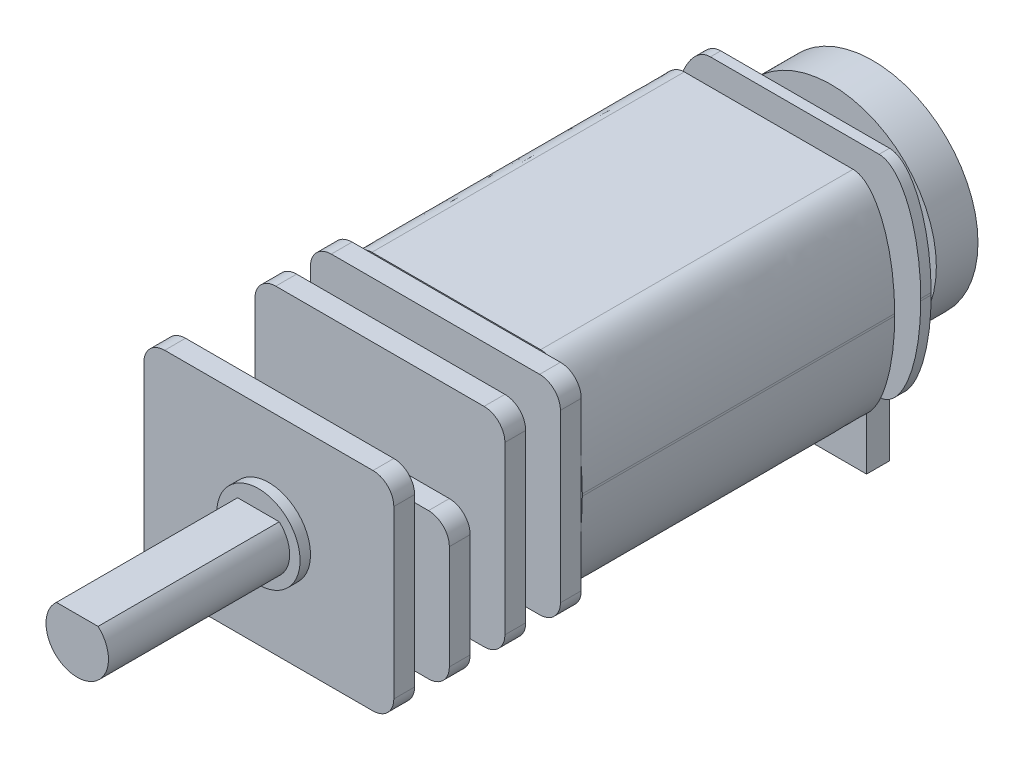
SolidWorks part; units mm, degrees
note: The reader was unsure of these and kept them because the rebuilt part matched: shared geometry of "Sketch1<3>", "Sketch2<3>", "Sketch2<5>".
ref_plane "Front Plane" through (0, 0, 0) normal (0, 0, 1) x (1, 0, 0)
ref_plane "Top Plane" through (0, 0, 0) normal (0, 1, 0) x (1, 0, 0)
ref_plane "Right Plane" through (0, 0, 0) normal (1, 0, 0) x (0, 0, -1)
sketch "Sketch1" plane through (0, 0, 0) normal (0, 0, 1) x (1, 0, 0)
  line L0 (1, 1.118) -> (-1, 1.118)
  circle A0 centre (0, 0) radius 1.5
  circle A1 centre (0, 0) radius 0.5
  dimension "D1" = 3
  dimension "D3" = 1
  dimension "D2" = 2
extrude "Boss-Extrude1" add sketch "Sketch1" along normal blind 8.7 contours L0 A0 | A1
extrude "Boss-Extrude3" add sketch "Sketch1<3>" against normal blind 38.2 from surface at 8.7 contours A1 starting at face at (0, -0.191, 8.7)
sketch "Sketch1<3>" plane through (0, 0, 0) normal (0, 0, 1) x (1, 0, 0) same geometry as "Sketch1"
sketch "Sketch2" plane through (0, 0, 0) normal (1, 0, 0) x (0, 0, -1)
  line L0 (0, 0) -> (0.5, 5) construction
  line L1 (0.5, 5) -> (1.5, 5)
  line L2 (0.5, 5) -> (0.5, -5)
  line L3 (0.5, -5) -> (1.5, -5)
  line L4 (1.5, 5) -> (1.5, -5)
  line L5 (6.8333, 5) -> (5.8333, 5)
  line L6 (6.8333, 5) -> (6.8333, -5)
  line L7 (6.8333, -5) -> (5.8333, -5)
  line L8 (5.8333, 5) -> (5.8333, -5)
  line L9 (8.5, 5) -> (9.5, 5)
  line L10 (8.5, 5) -> (8.5, -5)
  line L11 (8.5, -5) -> (9.5, -5)
  line L12 (9.5, 5) -> (9.5, -5)
  line L13 (3.1667, 2) -> (4.1667, 2)
  line L14 (3.1667, 2) -> (3.1667, -5)
  line L15 (3.1667, -5) -> (4.1667, -5)
  line L16 (4.1667, 2) -> (4.1667, -5)
  line L17 (0, -1.5) -> (0, 1.118) construction
  line L18 (0, 0) -> (0.5, -5) construction
  line L19 (27.5, 0) -> (0, 0) construction
  line L20 (27.5, 5.05) -> (29.5, 5.05)
  line L21 (27.5, 5.05) -> (27.5, 0)
  line L22 (27.5, 0) -> (29.5, 0)
  line L23 (29.5, 5.05) -> (29.5, 0)
  line L24 (25.75, 5.05) -> (26.25, 5.05)
  line L25 (25.75, 5.05) -> (25.75, -5.05)
  line L26 (25.75, -5.05) -> (26.25, -5.05)
  line L27 (26.25, 5.05) -> (26.25, -5.05)
  line L28 (9.5, 5.05) -> (24.5, 5.05)
  line L29 (9.5, 5.05) -> (9.5, -5.05)
  line L30 (9.5, -5.05) -> (24.5, -5.05)
  line L32 (24.5, 5.05) -> (25.75, 5.05) construction
  line L33 (26.25, 5.05) -> (27.5, 5.05) construction
  line L34 (1.5, -5) -> (3.1667, -5) construction
  line L35 (4.1667, -5) -> (5.8333, -5) construction
  line L36 (6.8333, -5) -> (8.5, -5) construction
  line L37 (24.5, 5.05) -> (24.5, 0)
  line L38 (24.5, 0) -> (24.5, -5.05)
  point P32 (7.6663, 5)
  dimension "D1" = 9
  dimension "D2" = 1
  dimension "D3" = 10
  dimension "D4" = 38.2
  dimension "D5" = 5
  dimension "D6" = 15
  dimension "D7" = 0.5
  dimension "D8" = 2
  dimension "D9" = 7
  dimension "D10" = 10.1
extrude "Boss-Extrude4" add sketch "Sketch2<3>" along normal mid plane 12.1
sketch "Sketch2<3>" plane through (0, 0, 0) normal (1, 0, 0) x (0, 0, -1) same geometry as "Sketch2"
fillet "Fillet2" radius 2 8 edges at (-6.05, -5.05, -17) (-6.05, 5.05, -17) (6.05, -5.05, -17) (6.05, 5.05, -17) (-6.05, -5.05, -26) (-6.05, 5.05, -26) (6.05, -5.05, -26) (6.05, 5.05, -26)
extrude "Boss-Extrude2" add sketch "Sketch2" along normal mid plane 12 contours L4 L1 L2 L3 | L16 L13 L14 L15 | L12 L9 L10 L11 | L8 L7 L6 L5
fillet "Fillet1" radius 1 16 edges at (-6, 5, -1) (6, 5, -1) (-6, -5, -1) (-6, -5, -3.6667) (-6, -5, -6.3333) (-6, -5, -9) (-6, 5, -9) (-6, 5, -6.3333) (-6, 2, -3.6667) (6, 5, -9) (6, 5, -6.3333) (6, 2, -3.6667) (6, -5, -9) (6, -5, -6.3333) (6, -5, -3.6667) (6, -5, -1)
revolve "Revolve1" add sketch "Sketch2<5>" angle 360 about L22
sketch "Sketch2<5>" plane through (0, 0, 0) normal (1, 0, 0) x (0, 0, -1) same geometry as "Sketch2"
sketch "Sketch3" plane through (0, 0, -0.5) normal (0, 0, 1) x (1, 0, 0)
  circle A0 centre (0, 0) radius 2
  dimension "D1" = 4
extrude "Boss-Extrude5" add sketch "Sketch3" along normal up to surface (0.5 mm away) up to face at (0.5, 0, 0)
sketch "Sketch4" plane through (0, 0, -25.75) normal (0, 0, 1) x (1, 0, 0)
  line L0 (-4, -4) -> (0, 0) construction
  line L1 (-4, -4) -> (4, -4)
  line L2 (-4, -4) -> (-4, -8)
  line L3 (-4, -8) -> (4, -8)
  line L4 (4, -4) -> (4, -8)
  line L5 (0, 0) -> (4, -4) construction
  line M10 (-4.05, -5.05) -> (4.05, -5.05)
  dimension "D1" = 8
  dimension "D2" = 4
  dimension "D3" = 4
extrude "Boss-Extrude6" add sketch "Sketch4" along normal mid plane 1.1 contours L4 L2 L3 M10 | L4 L1 L2 M10
